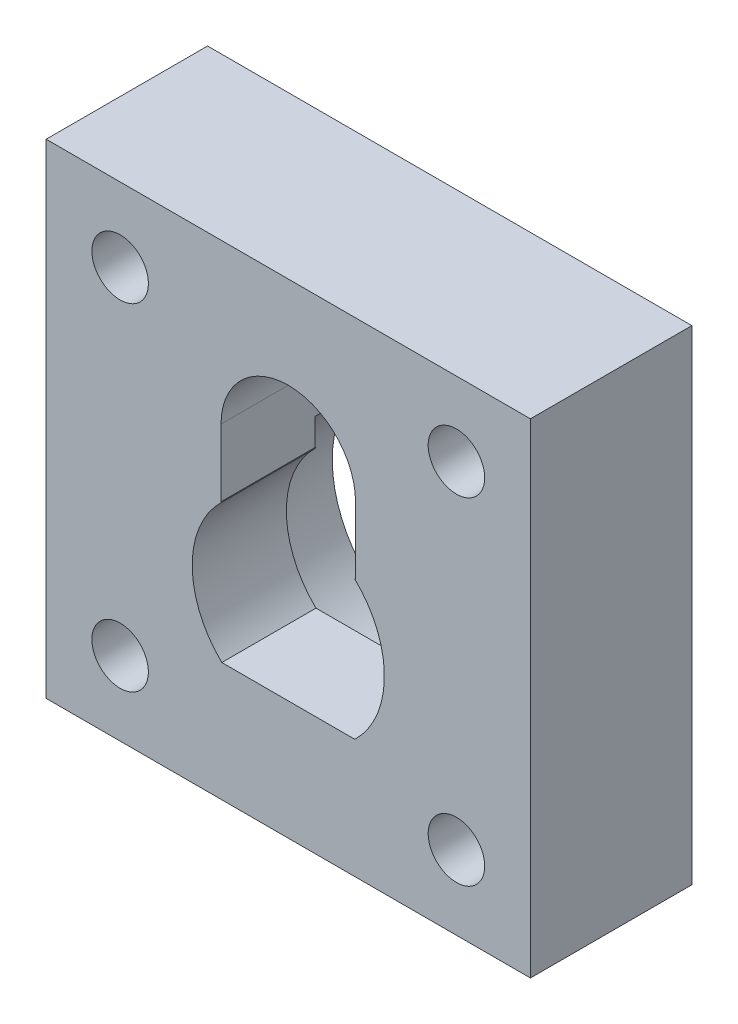
SolidWorks part; units mm, degrees
ref_plane "Front Plane" through (0, 0, 0) normal (0, 0, 1) x (1, 0, 0)
ref_plane "Top Plane" through (0, 0, 0) normal (0, 1, 0) x (1, 0, 0)
ref_plane "Right Plane" through (0, 0, 0) normal (1, 0, 0) x (0, 0, -1)
sketch "Sketch1" plane through (0, 0, 0) normal (0, 0, 1) x (1, 0, 0)
  line L1 (18, -18) -> (-18, -18)
  line L2 (18, -18) -> (18, 18)
  line L3 (18, 18) -> (-18, 18)
  line L4 (-18, -18) -> (-18, 18)
  line L5 (18, -18) -> (-18, 18) construction
  line L6 (18, 18) -> (-18, -18) construction
  point P0 (0, 0)
  dimension "D1" = 36
  dimension "D2" = 36
extrude "Boss-Extrude1" add sketch "Sketch1" along normal blind 12
sketch "Sketch2" plane through (0, 0, 0) normal (0, 0, -1) x (-1, 0, 0)
  line L1 (18, -18) -> (-18, -18) construction
  line L3 (18, 18) -> (18, -18) construction
  circle A0 centre (0, -4) radius 8.7312
  dimension "D1" = 17.4625
  dimension "D3" = 5.2688
  dimension "D4" = 9.2687
  dimension "D2" = 4
extrude "Cut-Extrude1" cut sketch "Sketch2" against normal blind 5
sketch "Sketch3" plane through (0, 0, 5) normal (0, 0, -1) x (-1, 0, 0)
  line L0 (-4.9411, 1.1594) -> (4.9411, 1.1594)
  line L1 (-4.9411, -9.1594) -> (4.9411, -9.1594)
  line L2 (-7.1437, -4) -> (7.1437, -4) construction
  arc A0 (-4.9411, 1.1594) -> (-4.9411, -9.1594) centre (0, -4) ccw
  circle A1 centre (0, -4) radius 8.7312 construction
  arc A2 (4.9411, -9.1594) -> (4.9411, 1.1594) centre (0, -4) ccw
  dimension "D1" = 14.2875
  dimension "D2" = 10.3187
extrude "Cut-Extrude2" cut sketch "Sketch3" against normal up to next
sketch "Sketch4" plane through (0, 0, 0) normal (0, 0, -1) x (-1, 0, 0)
  line L0 (4.9411, 1.1594) -> (-4.9411, 1.1594) construction
  line L1 (-5, 6.1594) -> (-5, 1.1594)
  line L2 (5, 6.1594) -> (5, 1.1594)
  line L3 (-5, 1.1594) -> (5, 1.1594)
  arc A0 (5, 6.1594) -> (-5, 6.1594) centre (0, 6.1594) ccw
  dimension "D1" = 10
extrude "Cut-Extrude3" cut sketch "Sketch4" against normal up to next
hole_wizard "M5x0.8 Tapped Hole1" positions "Sketch7" profile "Sketch6" tap size "M5x0.8" standard "ANSI Metric" end condition through all
sketch "Sketch7" plane through (0, 0, 12) normal (0, 0, 1) x (1, 0, 0)
  line L0 (-12.5, 12.5) -> (12.5, 12.5) construction
  line L1 (12.5, 12.5) -> (12.5, -12.5) construction
  point P0 (-12.5, -12.5)
  point P2 (12.5, -12.5)
  point P4 (12.5, 12.5)
  point P6 (-12.5, 12.5)
  point P13 (0, 12.5)
  point P15 (12.5, 0)
  dimension "D1" = 25
  dimension "D2" = 25
sketch "Sketch6" plane through (-12.5, -12.5, 12) normal (1, 0, 0) x (0, -1, 0)
  line L0 (0, 0) -> (0, 12)
  line L1 (0, 12) -> (2.1, 12)
  line L2 (2.1, 12) -> (2.1, 0)
  line L5 (2.1, 0) -> (0, 0)
  line L11 (0, -6.35) -> (0, 107.95) construction
  dimension "Thru Tap Drill Dia." = 4.2
  dimension "Thru Tap Drill Depth" = 12
